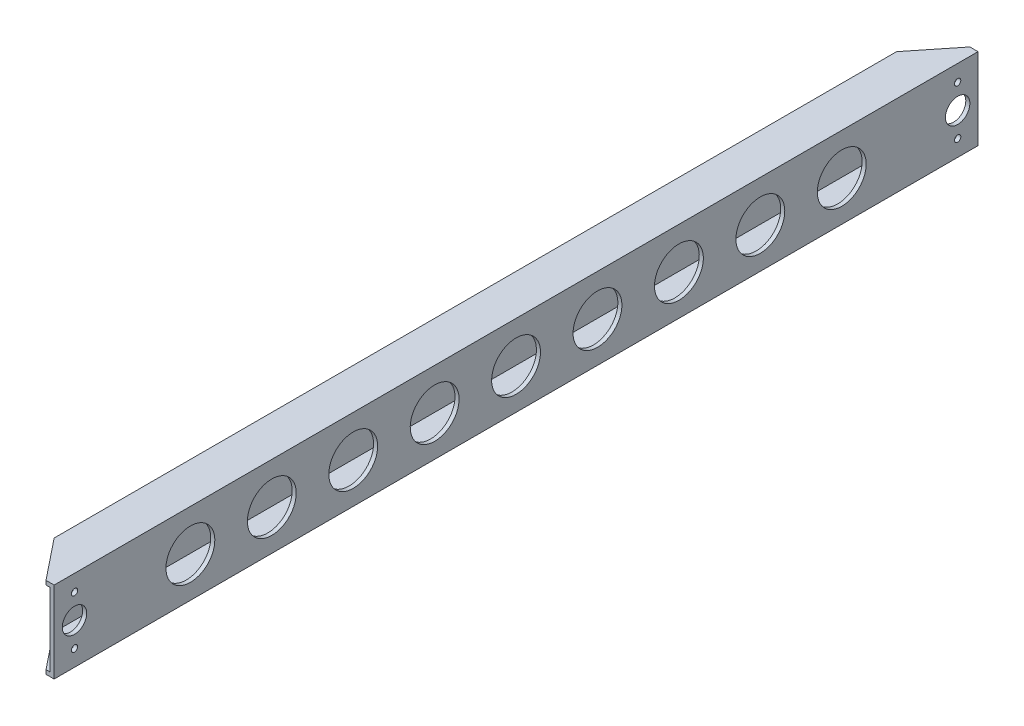
SolidWorks part; units mm, degrees
ref_plane "Front Plane" through (0, 0, 0) normal (0, 0, 1) x (1, 0, 0)
ref_plane "Top Plane" through (0, 0, 0) normal (0, 1, 0) x (1, 0, 0)
ref_plane "Right Plane" through (0, 0, 0) normal (1, 0, 0) x (0, 0, -1)
sketch "Sketch1" plane through (0, 0, 0) normal (0, 0, 1) x (1, 0, 0)
  line L1 (-12.1647, 2.5103) -> (19.5853, 2.5103)
  line L2 (-12.1647, 2.5103) -> (-12.1647, -60.9897)
  line L3 (-12.1647, -60.9897) -> (19.5853, -60.9897)
  line L4 (19.5853, 2.5103) -> (19.5853, -60.9897)
  line L5 (-8.9897, -0.6647) -> (16.4103, -0.6647)
  line L6 (-8.9897, -0.6647) -> (-8.9897, -57.8147)
  line L7 (-8.9897, -57.8147) -> (16.4103, -57.8147)
  line L8 (16.4103, -0.6647) -> (16.4103, -57.8147)
  dimension "D1" = 63.5
  dimension "D2" = 31.75
  dimension "D3" = 3.175
  dimension "D4" = 3.175
  dimension "D5" = 3.175
  dimension "D6" = 3.175
extrude "Boss-Extrude1" add sketch "Sketch1" along normal blind 720.4964
sketch "Sketch2" plane through (0, 2.5103, 0) normal (0, 1, 0) x (1, 0, 0)
  line L0 (13.2353, 0) -> (-12.1647, -31.75)
  line L1 (19.5853, 0) -> (-12.1647, 0) construction
  line L2 (-12.1647, -720.4964) -> (-12.1647, 0) construction
  line L3 (-12.1647, -31.75) -> (-12.1647, 0)
  line L4 (-12.1647, 0) -> (13.2353, 0)
  line L5 (19.5853, -720.4964) -> (19.5853, 0) construction
  line L6 (19.5853, -360.2482) -> (-12.1647, -360.2482)
  line L7 (-12.1647, -720.4964) -> (13.2353, -720.4964)
  line L8 (-12.1647, -688.7464) -> (-12.1647, -720.4964)
  line L9 (13.2353, -720.4964) -> (-12.1647, -688.7464)
  line M4 (19.5853, 0) -> (-12.1647, 0)
  line M5 (-12.1647, 0) -> (-12.1647, -720.4964)
  line M6 (-12.1647, -720.4964) -> (19.5853, -720.4964)
  dimension "D1" = 25.4
  dimension "D2" = 31.75
extrude "Cut-Extrude1" cut sketch "Sketch2" against normal up to surface (63.5 mm away) contours L0 M4 M5 | L9 M6 M5 region at (-3.6981, 2.5103, 709.9131) region at (-3.6981, 2.5103, 10.5833) up to face at (3.7103, -60.9897, 360.2482)
sketch "Sketch3" plane through (16.4103, 0, 0) normal (-1, 0, 0) x (0, 0, 1)
  line L0 (0, -57.8147) -> (0, -0.6647) construction
  line L1 (0, 2.5103) -> (31.75, 2.5103) construction
  line L2 (0, -29.2397) -> (27.7812, -29.2397)
  line L3 (27.7812, -57.8147) -> (27.7812, -0.6647) construction
  line L4 (360.2482, 2.5103) -> (360.2482, -60.9897)
  line L5 (720.4964, -29.2397) -> (692.7151, -29.2397)
  line L6 (688.7464, 2.5103) -> (31.75, 2.5103) construction
  line L7 (688.7464, -60.9897) -> (31.75, -60.9897) construction
  circle A0 centre (15.875, -29.2397) radius 9.525
  circle A1 centre (704.6214, -29.2397) radius 9.525
  point P0 (15.875, -10.1897)
  point P9 (15.875, -48.2897)
  point P22 (704.6214, -48.2897)
  point P23 (704.6214, -10.1897)
  dimension "D1" = 15.875
  dimension "D2" = 12.7
hole_wizard "#10 (0.1935) Diameter Hole1" positions "3DSketch1" profile "Sketch4" hole size "#10" standard "ANSI Inch" end condition through all
sketch3d "3DSketch1"
  point P0 (16.4103, -10.1897, 15.875)
  point P3 (16.4103, -48.2897, 15.875)
  point P6 (16.4103, -10.1897, 704.6214)
  point P9 (16.4103, -48.2897, 704.6214)
sketch "Sketch4" plane through (16.4103, -10.1897, 15.875) normal (0, 1, 0) x (0, 0, 1)
  line L0 (0, 0) -> (0, 3.175)
  line L1 (0, 3.175) -> (2.4574, 3.175)
  line L2 (2.4574, 3.175) -> (2.4574, 0)
  line L5 (2.4574, 0) -> (0, 0)
  line L11 (0, -6.35) -> (0, 107.95) construction
  dimension "Thru Hole Dia." = 4.9149
  dimension "Thru Hole Depth" = 3.175
extrude "Cut-Extrude2" cut sketch "Sketch3" against normal up to surface (3.175 mm away) contours A0 | A1 up to face at (19.5853, -10.1897, 18.3325)
sketch "Sketch5" plane through (-12.1647, 0, 0) normal (-1, 0, 0) x (0, 0, 1)
  line L0 (31.75, -60.9897) -> (31.75, 2.5103) construction
  circle A0 centre (106.2482, -29.7597) radius 19.05
  circle A1 centre (169.7482, -29.7597) radius 19.05
  circle A2 centre (233.2482, -29.7597) radius 19.05
  circle A3 centre (296.7482, -29.7597) radius 19.05
  circle A4 centre (360.2482, -29.7597) radius 19.05
  circle A5 centre (423.7482, -29.7597) radius 19.05
  circle A6 centre (487.2482, -29.7597) radius 19.05
  circle A7 centre (550.7482, -29.7597) radius 19.05
  circle A8 centre (614.2482, -29.7597) radius 19.05
  point P5 (31.75, -29.2397)
  dimension "D1" = 38.1
  dimension "D2" = 74.4982
  dimension "D3" = 9
extrude "Cut-Extrude3" cut sketch "Sketch5" against normal up to surface (31.75 mm away) up to face at (19.5853, -38.7647, 704.6214)
